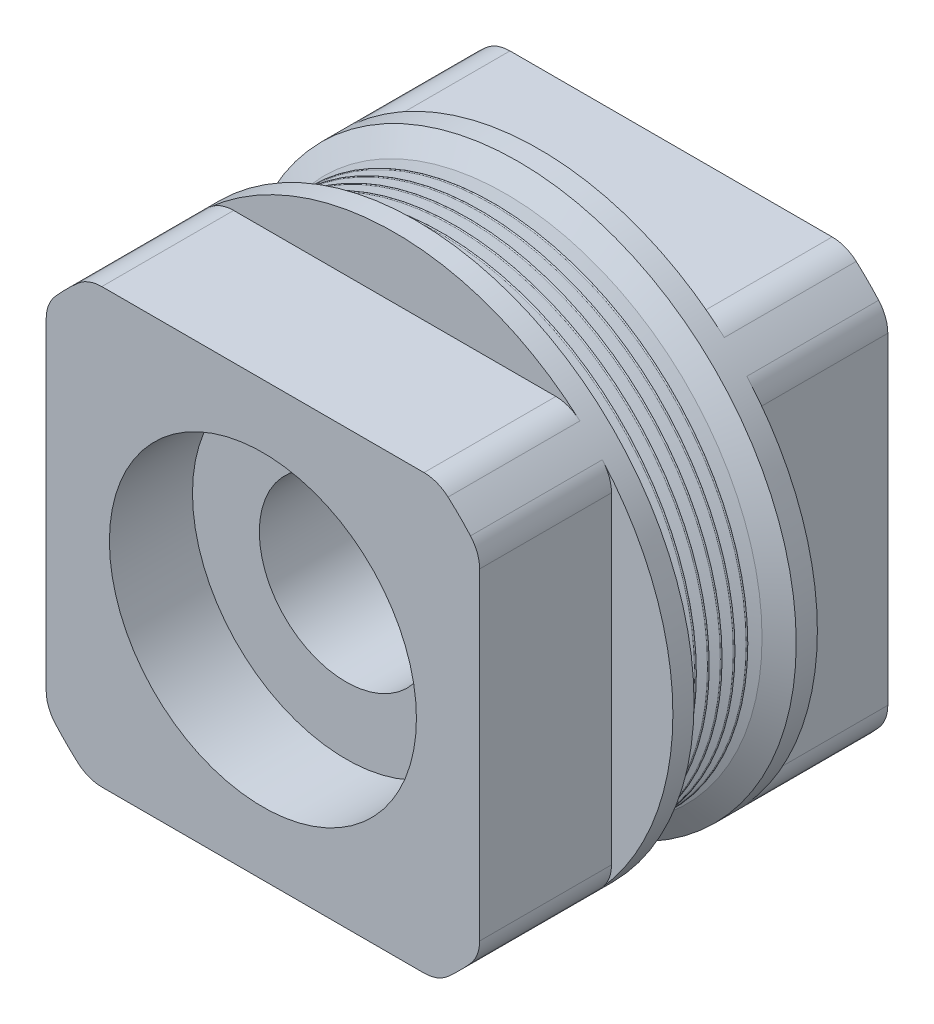
SolidWorks part; units mm, degrees
material "AISI 4340 Aço recozido"
ref_plane "Plano frontal" through (0, 0, 0) normal (0, 0, 1) x (1, 0, 0)
ref_plane "Plano superior" through (0, 0, 0) normal (0, 1, 0) x (1, 0, 0)
ref_plane "Plano direito" through (0, 0, 0) normal (1, 0, 0) x (0, 0, -1)
sketch "Esboço2" plane through (0, 0, 0) normal (0, 0, 1) x (1, 0, 0)
  line L1 (-55, -60) -> (55, -60)
  line L2 (-60, -55) -> (-60, 55)
  line L3 (-55, 60) -> (55, 60)
  line L4 (60, -55) -> (60, 55)
  line L5 (-60, -60) -> (60, 60) construction
  line L6 (-60, 60) -> (60, -60) construction
  arc A0 (-55, -60) -> (-60, -55) centre (-55, -55) cw
  arc A1 (55, -60) -> (60, -55) centre (55, -55) ccw
  arc A2 (55, 60) -> (60, 55) centre (55, 55) cw
  arc A3 (-60, 55) -> (-55, 60) centre (-55, 55) cw
  circle A4 centre (0, 0) radius 42.5
  circle A5 centre (0, 0) radius 25
  point P0 (0, 0)
  point P21 (0, 0)
  dimension "D2" = 5
  dimension "D3" = 85
  dimension "D4" = 50
  dimension "D1" = 120
sketch "Esboço3" plane through (0, 0, 0) normal (1, 0, 0) x (0, 0, -1)
  line L0 (20, 0) -> (20, 77)
  line L1 (20, 77) -> (14.1441, 77)
  line L3 (8.4302, 67.4004) -> (7.3549, 70.3546)
  line L4 (6.8851, 70.3546) -> (5.8098, 67.4004)
  line L5 (4.8702, 67.4004) -> (3.7949, 70.3546)
  line L6 (3.3251, 70.3546) -> (2.2498, 67.4004)
  line L7 (1.3102, 67.4004) -> (0.2349, 70.3546)
  line L8 (-0.2349, 70.3546) -> (-1.3102, 67.4004)
  line L9 (-2.2498, 67.4004) -> (-3.3251, 70.3546)
  line L10 (-3.7949, 70.3546) -> (-4.8702, 67.4004)
  line L11 (-5.8098, 67.4004) -> (-6.8851, 70.3546)
  line L12 (-7.3549, 70.3546) -> (-8.4302, 67.4004)
  line L14 (-14.1441, 77) -> (-20, 77)
  line L15 (-20, 77) -> (-20, 0)
  line L16 (-20, 0) -> (20, 0)
  line L17 (-10.68, 71) -> (10.68, 71) construction
  line L18 (-20, 77) -> (-20, 200)
  line L19 (0, 0) -> (51.063, 0) construction
  line L20 (-9.3698, 67.4004) -> (-10.68, 71)
  line L21 (-10.68, 71) -> (-14.1441, 77)
  line L22 (9.3698, 67.4004) -> (10.68, 71)
  line L23 (10.68, 71) -> (14.1441, 77)
  line L24 (-20, 200) -> (20, 200)
  line L25 (14.1441, 77) -> (20, 87.1427)
  line L26 (20, 87.1427) -> (20, 77)
  line L27 (-14.1441, 77) -> (-20, 87.1427)
  line L28 (-20, 87.1427) -> (-20, 77)
  line L29 (20, 200) -> (20, 77)
  line L30 (20, 77) -> (75, 77)
  line L31 (75, 77) -> (75, 127)
  line L32 (75, 127) -> (-75, 127)
  line L33 (-75, 127) -> (-75, 77)
  line L34 (-75, 77) -> (-20, 77)
  arc A0 (-6.8851, 70.3546) -> (-7.3549, 70.3546) centre (-7.12, 70.269) ccw
  arc A1 (-3.3251, 70.3546) -> (-3.7949, 70.3546) centre (-3.56, 70.269) ccw
  arc A2 (0.2349, 70.3546) -> (-0.2349, 70.3546) centre (0, 70.269) ccw
  arc A3 (3.7949, 70.3546) -> (3.3251, 70.3546) centre (3.56, 70.269) ccw
  arc A4 (7.3549, 70.3546) -> (6.8851, 70.3546) centre (7.12, 70.269) ccw
  arc A5 (9.3698, 67.4004) -> (8.4302, 67.4004) centre (8.9, 67.5714) cw
  arc A6 (5.8098, 67.4004) -> (4.8702, 67.4004) centre (5.34, 67.5714) cw
  arc A7 (2.2498, 67.4004) -> (1.3102, 67.4004) centre (1.78, 67.5714) cw
  arc A8 (-1.3102, 67.4004) -> (-2.2498, 67.4004) centre (-1.78, 67.5714) cw
  arc A9 (-4.8702, 67.4004) -> (-5.8098, 67.4004) centre (-5.34, 67.5714) cw
  arc A10 (-8.4302, 67.4004) -> (-9.3698, 67.4004) centre (-8.9, 67.5714) cw
  point P2 (-7.12, 71)
  point P24 (-7.12, 71)
  point P27 (0, 0)
  point P31 (-71.4427, 75.5)
  point P32 (0, 127)
  point P36 (-7.12, 71)
  point P39 (-3.56, 71)
  point P42 (0, 71)
  point P45 (3.56, 71)
  point P48 (7.12, 71)
  point P54 (5.34, 66.1095)
  point P57 (1.78, 66.1095)
  point P60 (-1.78, 66.1095)
  point P63 (-5.34, 66.1095)
  dimension "D1" = 0.5
  dimension "D2" = 0.25
  dimension "D3" = 40
  dimension "D4" = 40
  dimension "D5" = 20
  dimension "D6" = 3.56
  dimension "D7" = 60
  dimension "D8" = 30
  dimension "D9" = 142
  dimension "D10" = 6
  dimension "D11" = 200
  dimension "D12" = 150
  dimension "D13" = 50
extrude "Ressalto-extrusão1" add sketch "Esboço2" along normal mid plane 113 contours L3 A2 L4 A1 L1 A0 L2 A3
revolve "Revolução1" add sketch "Esboço3" angle 360 about L16 region at (0, 36.1147, 0)
revolve "Corte-Revolução1" cut sketch "Esboço3<4>" angle 360 about L19 region at (0, 80.3809, -18.048) region at (0, 102, -47.5) region at (0, 99.8952, 0) region at (0, 80.3809, 18.048) region at (0, 102, 47.5)
sketch "Esboço3<4>" plane through (0, 0, 0) normal (1, 0, 0) x (0, 0, -1) same geometry as "Esboço3"
sketch "Esboço4" plane through (0, 0, 0) normal (0, 0, 1) x (1, 0, 0)
  circle A0 centre (0, 0) radius 24
  circle A1 centre (0, 0) radius 42.5
  dimension "D1" = 85
  dimension "D2" = 48
extrude "Corte-extrusão1" cut sketch "Esboço4" along normal offset from surface (23 mm away) 23 from surface contours A1 up to face at (0, 0, -56.5) starting at face at (0, 0, -56.5)
extrude "Corte-extrusão2" cut sketch "Esboço4<4>" against normal blind 23 from surface contours A1 starting at face at (0, 0, 56.5)
sketch "Esboço4<4>" plane through (0, 0, 0) normal (0, 0, 1) x (1, 0, 0) same geometry as "Esboço4"
extrude "Corte-extrusão3" cut sketch "Esboço4<5>" against normal through all both and the other way through all contours A0
sketch "Esboço4<5>" plane through (0, 0, 0) normal (0, 0, 1) x (1, 0, 0) same geometry as "Esboço4"
fillet "Filete1" [suppressed] radius 6
fillet "Filete3" radius 10 16 edges at (-60, 48.2597, 38.25) (-48.2597, 60, 38.25) (48.2597, 60, 38.25) (60, 48.2597, 38.25) (60, -48.2597, 38.25) (48.2597, -60, 38.25) (-60, -48.2597, 38.25) (-48.2597, -60, 38.25) (-60, -48.2597, -38.25) (-48.2597, 60, -38.25) (-60, 48.2597, -38.25) (-48.2597, -60, -38.25) (48.2597, -60, -38.25) (60, -48.2597, -38.25) (60, 48.2597, -38.25) (48.2597, 60, -38.25)
hole_wizard "Broca de rosquear para tarraxa de M16x2.01" positions "Esboço7" profile "Esboço8" hole size "M16x2.0" standard "Ansi Metric"
sketch "Esboço7" plane through (0, 0, -56.5) normal (0, 0, -1) x (-1, 0, 0)
  line L1 (-42.5, -42.5) -> (42.5, -42.5)
  line L2 (-42.5, -42.5) -> (-42.5, 42.5)
  line L3 (-42.5, 42.5) -> (42.5, 42.5)
  line L4 (42.5, -42.5) -> (42.5, 42.5)
  line L5 (-42.5, -42.5) -> (42.5, 42.5) construction
  line L6 (-42.5, 42.5) -> (42.5, -42.5) construction
  point P18 (42.5, 42.5)
  point P83 (-42.5, -42.5)
  point P84 (-42.5, 42.5)
  point P85 (42.5, -42.5)
  point P99 (0, 0)
  dimension "D1" = 85
sketch "Esboço8" plane through (-42.5, 42.5, -56.5) normal (1, 0, 0) x (0, 1, 0)
  line L0 (0, 0) -> (0, 34.206)
  line L1 (0, 34.206) -> (7, 30)
  line L2 (7, 30) -> (7, 0)
  line L5 (7, 0) -> (0, 0)
  line L10 (0, 34.206) -> (-7, 30) construction
  line L11 (0, -6.35) -> (0, 107.95) construction
  dimension "Hole Dia." = 14
  dimension "Hole Depth" = 30
  dimension "Drill Angle" = 118
equation "\"arma-espessura\"= 50                                    'disco arma - espessura disco arma"
equation "\"rolamento_D-ext\"= 85                                   'rolamento arma - diametro externo"
equation "\"rolamento_d-int\"= 45                                   'rolamento arma - diametro interno"
equation "\"rolamento_b-esp\"= 23                                   'rolamento arma - espessura"
equation "\"eixo_diam\"= \"rolamento_d-int\"                          'eixo arma - diametro"
equation "\"camisa_largura\"=120                                    'camisa arma - tamanho do lado"
equation "\"camisa_raio\"=5                                        'camisa arma - raio canto interno"
equation "\"D1@Esboço2\"=\"camisa_largura\""
equation "\"D2@Esboço2\"=\"camisa_raio\""
equation "\"D3@Esboço2\"=\"rolamento_D-ext\""
equation "\"D4@Esboço2\"=5+\"eixo_diam\""
equation "\"D1\" = \"rolamento_b-esp\" +  ( \"arma-espessura\" - \"rolamento_b-esp\" )  / 2"
equation "\"polia_diam_eff\" = 142"
equation "\"D9@Esboço3\"=\"polia_diam_eff\""
equation "\"escala\" = 1                                            'projeto - escala geral"
equation "\"escala_disco-arma\"= 2.9                               'disco arma - escala geometria disco arma"
equation "\"arma_eixo-furo_folga\" = 4                              'arma - folga entre furo arma e eixo"
equation "\"arma_rebaixo-camisa_raio\" = 16      'raio do rebaixo da camisa da arma "
equation "\"arma_rebaixo-camisa_b\"= \"rolamento_b-esp\" + (\"arma-espessura\"-\"rolamento_b-esp\")/2        'disco arma - profundidade rebaixo camisa"
equation "\"camisa_rebaixo_rolamento\" = 1 * \"rolamento_b-esp\""
equation "\"D1@Ressalto-extrusão1\"=\"camisa_comprimento-centro\""
equation "\"polia_espessura\" = 40  "
equation "\"D3@Esboço3\"=\"polia_espessura\""
equation "\"D1@Esboço4\"=\"rolamento_D-ext\""
equation "\"D2@Esboço4\"=\"rolamento_d-int\"+3"
equation "\"camisa_comprimento-centro\" = 2*(\"arma_rebaixo-camisa_b\")+\"polia_espessura\"   "
equation "\"D1@Corte-extrusão1\"=\"rolamento_b-esp\""
equation "\"D1@Corte-extrusão2\"=\"camisa_rebaixo_rolamento\""
